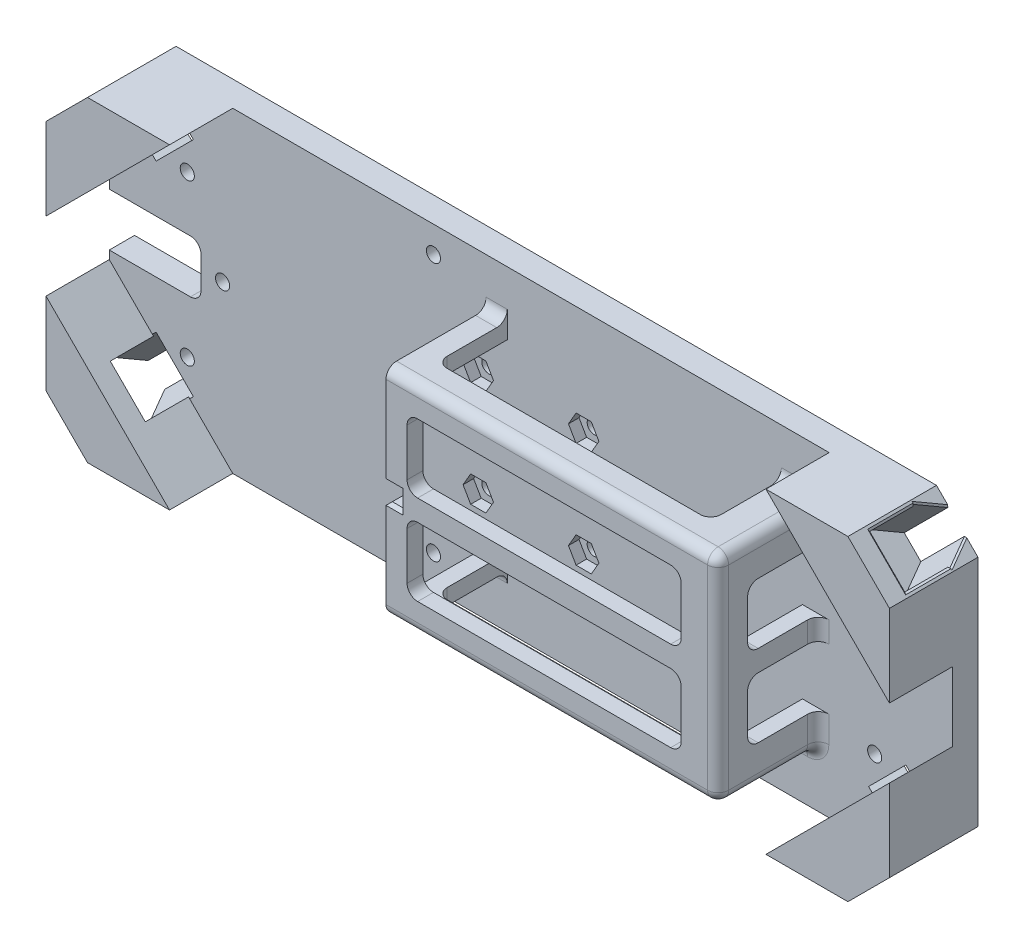
SolidWorks part; units mm, degrees
ref_plane "Front Plane" through (0, 0, 0) normal (0, 0, 1) x (1, 0, 0)
ref_plane "Top Plane" through (0, 0, 0) normal (0, 1, 0) x (1, 0, 0)
ref_plane "Right Plane" through (0, 0, 0) normal (1, 0, 0) x (0, 0, -1)
sketch "Sketch1" plane through (10.8587, 0, 0) normal (0, 0, 1) x (1, 0, 0)
  line L0 (-52.705, 21.59) -> (48.895, 21.59)
  line L1 (52.705, -25.4) -> (-52.705, -25.4)
  line L2 (52.705, -25.4) -> (52.705, 25.4)
  line L3 (52.705, 25.4) -> (-52.705, 25.4)
  line L4 (-52.705, -25.4) -> (-52.705, 25.4)
  line L5 (52.705, -25.4) -> (-52.705, 25.4) construction
  line L6 (52.705, 25.4) -> (-52.705, -25.4) construction
  line L7 (48.895, 21.59) -> (48.895, -22.86)
  line L8 (48.895, -22.86) -> (-52.705, -22.86)
  line L9 (-52.705, 13.97) -> (-6.985, 13.97)
  line L10 (-6.985, 13.97) -> (-6.985, -6.35)
  line L11 (-6.985, -6.35) -> (-52.705, -6.35)
  point P0 (0, 0)
  dimension "D1" = 105.41
  dimension "D2" = 50.8
  dimension "D3" = 101.6
  dimension "D4" = 44.45
  dimension "D5" = 3.81
  dimension "D6" = 45.72
  dimension "D7" = 20.32
  dimension "D8" = 7.62
extrude "Boss-Extrude1" add sketch "Sketch1" along normal blind 27.432 contours L7 L8 L4 L1 L2 L3 L0 region at (-40.6761, 23.495, 0)
extrude "Boss-Extrude2" add sketch "Sketch1<3>" along normal blind 5.08 contours L10 L11 L4 L8 L7 L0 L9 region at (16.19, -1.7862, 0)
sketch "Sketch1<3>" plane through (10.8587, 0, 0) normal (0, 0, 1) x (1, 0, 0) same geometry as "Sketch1"
sketch "Sketch4" plane through (10.8587, 0, 5.08) normal (0, 0, 1) x (1, 0, 0)
  line L0 (-52.705, 21.59) -> (48.895, 21.59) construction
  line L1 (-44.7859, 21.59) -> (-47.9241, 21.59)
  line L2 (-47.9241, 21.59) -> (-49.4932, 18.8722)
  line L3 (-49.4932, 18.8722) -> (-47.9241, 16.1544)
  line L4 (-47.9241, 16.1544) -> (-44.7859, 16.1544)
  line L5 (-44.7859, 16.1544) -> (-43.2168, 18.8722)
  line L6 (-43.2168, 18.8722) -> (-44.7859, 21.59)
  line L7 (-52.705, 13.97) -> (-52.705, 21.59) construction
  line L8 (-13.3987, 22.7847) -> (-13.3987, -11.3368) construction
  line L9 (21.1266, 16.1544) -> (17.9884, 16.1544)
  line L10 (17.9884, 16.1544) -> (16.4193, 18.8722)
  line L11 (16.4193, 18.8722) -> (17.9884, 21.59)
  line L12 (17.9884, 21.59) -> (21.1266, 21.59)
  line L13 (21.1266, 21.59) -> (22.6958, 18.8722)
  line L14 (22.6958, 18.8722) -> (21.1266, 16.1544)
  line L15 (0, 0) -> (10.9329, 0) construction
  line L16 (22.6958, -18.8722) -> (21.1266, -16.1544)
  line L17 (21.1266, -21.59) -> (22.6958, -18.8722)
  line L18 (17.9884, -21.59) -> (21.1266, -21.59)
  line L19 (16.4193, -18.8722) -> (17.9884, -21.59)
  line L20 (17.9884, -16.1544) -> (16.4193, -18.8722)
  line L21 (21.1266, -16.1544) -> (17.9884, -16.1544)
  line L22 (-49.4932, -18.8722) -> (-47.9241, -16.1544)
  line L23 (-47.9241, -21.59) -> (-49.4932, -18.8722)
  line L24 (-43.2168, -18.8722) -> (-44.7859, -21.59)
  line L25 (-44.7859, -16.1544) -> (-43.2168, -18.8722)
  line L26 (-47.9241, -16.1544) -> (-44.7859, -16.1544)
  line L27 (-44.7859, -21.59) -> (-47.9241, -21.59)
  circle A0 centre (-46.355, 18.8722) radius 2.7178 construction
  circle A1 centre (-46.355, 18.8722) radius 1.524
  circle A2 centre (19.5575, 18.8722) radius 1.524
  circle A3 centre (-46.355, -18.8722) radius 1.524
  circle A4 centre (19.5575, -18.8722) radius 1.524
  dimension "D4" = 3.048
  dimension "D1" = 5.4356
  dimension "D2" = 6.35
  dimension "D3" = 2.54
extrude "Cut-Extrude1" cut sketch "Sketch4" against normal blind 2.286 contours L5 L6 L14 L2 L3 L4 A1 | L14 L13 L11 L10 L9 A2 | L26 L22 L23 L12 L24 L25 A3 | L16 L21 L20 L19 L12 L17 A4 region at (-33.2145, 20.1896, 5.08) region at (30.4163, 16.2374, 5.08) region at (32.698, -20.1896, 5.08) region at (-37.778, -17.5548, 5.08)
extrude "Cut-Extrude2" cut sketch "Sketch4<4>" against normal through all contours A1 | A2 | A3 | A4 region at (-35.4963, 18.8722, 5.08) region at (30.4163, 18.8722, 5.08) region at (-35.4963, -18.8722, 5.08) region at (30.4163, -18.8722, 5.08)
sketch "Sketch4<4>" plane through (10.8587, 0, 5.08) normal (0, 0, 1) x (1, 0, 0) same geometry as "Sketch4"
sketch "Sketch7" plane through (10.8587, 0, 27.432) normal (0, 0, 1) x (1, 0, 0)
  line L0 (0, 0) -> (-46.355, 0) construction
  line L1 (-52.705, 25.4) -> (52.705, 25.4)
  line L2 (-52.705, 25.4) -> (-52.705, 6.35)
  line L3 (-52.705, -25.4) -> (52.705, -25.4)
  line L4 (52.705, 25.4) -> (52.705, -25.4)
  line L5 (-52.705, 6.35) -> (-46.355, 6.35)
  line L7 (-52.705, -6.35) -> (-46.355, -6.35)
  line L8 (-46.355, 6.35) -> (-46.355, -6.35)
  line L9 (-52.705, -6.35) -> (-52.705, -25.4)
  line L10 (-28.575, 0) -> (-1035.3573, 0) construction
  point P11 (-46.355, 0)
  dimension "D1" = 12.7
  dimension "D2" = 6.35
extrude "Boss-Extrude3" add sketch "Sketch7" along normal blind 3.81
fillet "Fillet1" radius 2.54 5 edges at (10.8587, -25.4, 31.242) (63.5637, -25.4, 15.621) (63.5637, 0, 31.242) (63.5637, 25.4, 15.621) (10.8587, 25.4, 31.242)
chamfer "Chamfer3" distance 1.27 angle 45 9 edges at (-41.8463, 21.59, 16.256) (-41.8463, -22.86, 16.256) (-41.8463, 13.97, 27.432) (-41.8463, -14.605, 27.432) (-41.8463, -6.35, 29.337) (-38.6713, -6.35, 31.242) (-35.4963, 0, 31.242) (-38.6713, 6.35, 31.242) (-41.8463, 6.35, 29.337)
chamfer "Chamfer4" distance 0.254 angle 45 4 edges at (-33.9723, -18.8722, 0) (31.9403, -18.8722, 0) (-33.9723, 18.8722, 0) (31.9403, 18.8722, 0)
sketch "Sketch8" plane through (10.8587, 0, 5.08) normal (0, 0, 1) x (1, 0, 0)
  line L0 (-52.705, -7.62) -> (-52.705, -22.86) construction
  line L1 (48.895, 21.59) -> (-52.705, 21.59)
  line L2 (48.895, 21.59) -> (48.895, -22.86)
  line L3 (48.895, -22.86) -> (-52.705, -22.86)
  line L4 (-52.705, 21.59) -> (-52.705, -22.86)
  line L5 (48.895, -22.86) -> (-51.435, -22.86) construction
extrude "Cut-Extrude3" cut sketch "Sketch8" against normal up to surface (5.08 mm away) up to face at (-33.7183, -18.8722, 0)
chamfer "Chamfer5" distance 1.27 angle 45 2 edges at (-41.8463, -22.86, 2.54) (-41.8463, 21.59, 2.54)
sketch "Sketch9" plane through (10.8587, 0, 0) normal (0, 0, -1) x (-1, 0, 0)
  line L0 (-90.7413, 28.1) -> (-80.7413, 38.1)
  line L1 (-80.7413, -38.1) -> (102.4587, -38.1)
  line L2 (-90.7413, -28.1) -> (-90.7413, 28.1)
  line L3 (-80.7413, 38.1) -> (102.4587, 38.1)
  line L4 (112.4587, -28.1) -> (112.4587, 28.1)
  line L5 (-90.7413, -38.1) -> (112.4587, 38.1) construction
  line L6 (-90.7413, 38.1) -> (112.4587, -38.1) construction
  line L7 (-90.7413, -28.1) -> (-80.7413, -38.1)
  line L8 (102.4587, 38.1) -> (112.4587, 28.1)
  line L9 (102.4587, -38.1) -> (112.4587, -28.1)
  point P0 (10.8587, 0)
  dimension "D1" = 203.2
  dimension "D2" = 76.2
extrude "Boss-Extrude4" add sketch "Sketch9" along normal blind 6.096
fillet "Fillet2" radius 1.27 5 edges at (9.5887, -25.4, 0) (62.8198, -24.6561, 0) (63.5637, 0, 0) (62.8198, 24.6561, 0) (9.5887, 25.4, 0)
sketch "Sketch11" plane through (0, 0, 0) normal (0, 0, 1) x (1, 0, 0)
  line L0 (-101.6, 28.1) -> (-91.6, 38.1)
  line L1 (-91.6, 38.1) -> (-84.9257, 38.1)
  line L4 (-101.6, -28.1) -> (-101.6, 28.1) construction
  line L5 (-101.6, 21.4257) -> (-101.6, 28.1)
  line L6 (0, 0) -> (0, 53.0626) construction
  line L7 (-1000, 0) -> (0, 0) construction
  line L25 (-76.5885, 29.7628) -> (-93.2628, 13.0885)
  line L26 (-84.9257, 38.1) -> (-76.5885, 29.7628)
  line L28 (-101.6, 21.4257) -> (-93.2628, 13.0885)
  line L54 (0, -17.1831) -> (0, 17.1831) construction
  line L55 (84.9257, 38.1) -> (76.5885, 29.7628)
  line L56 (91.6, 38.1) -> (84.9257, 38.1)
  line L57 (101.6, 28.1) -> (91.6, 38.1)
  line L58 (101.6, 21.4257) -> (101.6, 28.1)
  line L59 (101.6, 21.4257) -> (93.2628, 13.0885)
  line L60 (76.5885, 29.7628) -> (93.2628, 13.0885)
  line L61 (17.1831, 0) -> (-17.1831, 0) construction
  line L62 (91.6, -38.1) -> (84.9257, -38.1)
  line L63 (101.6, -28.1) -> (91.6, -38.1)
  line L64 (101.6, -21.4257) -> (101.6, -28.1)
  line L65 (101.6, -21.4257) -> (93.2628, -13.0885)
  line L66 (76.5885, -29.7628) -> (93.2628, -13.0885)
  line L67 (84.9257, -38.1) -> (76.5885, -29.7628)
  line L68 (-84.9257, -38.1) -> (-76.5885, -29.7628)
  line L69 (-91.6, -38.1) -> (-84.9257, -38.1)
  line L70 (-101.6, -28.1) -> (-91.6, -38.1)
  line L71 (-101.6, -21.4257) -> (-101.6, -28.1)
  line L72 (-101.6, -21.4257) -> (-93.2628, -13.0885)
  line L73 (-76.5885, -29.7628) -> (-93.2628, -13.0885)
  dimension "D1" = 16.51
  dimension "D2" = 8.3372
extrude "Boss-Extrude5" [suppressed] add sketch "Sketch11" along normal blind 19.05
sketch "Sketch13" plane through (-64.85, 64.85, 0) normal (-0.7071, 0.7071, 0) x (0, 0, 1)
  line L0 (-6.096, -44.9013) -> (-6.096, -42.0708)
  line L1 (-6.096, -51.9723) -> (-6.096, -37.8302) construction
  line L2 (-6.096, -42.0708) -> (0, -38.5513)
  line L3 (0, -38.5513) -> (0, -51.2513)
  line L4 (0, -51.2513) -> (-6.096, -47.7318)
  line L5 (-6.096, -47.7318) -> (-6.096, -44.9013)
  dimension "D1" = 6.096
  dimension "D2" = 120
  dimension "D3" = 120
  dimension "D4" = 12.7
extrude "Cut-Extrude4" cut sketch "Sketch13" against normal blind 15.24
mirror "Mirror2" about plane through (0, 0, 0) normal (0, 1, 0) of "Cut-Extrude4"
mirror "Mirror3" about plane through (0, 0, 0) normal (1, 0, 0) of "Cut-Extrude4", "Mirror2"
chamfer "Chamfer7" distance 0.381 angle 45 8 edges at (99.8458, -29.8542, -3.048) (93.3542, -36.3458, -3.048) (93.3542, 36.3458, -3.048) (99.8458, 29.8542, -3.048) (-93.3542, 36.3458, -3.048) (-99.8458, 29.8542, -3.048) (-93.3542, -36.3458, -3.048) (-99.8458, -29.8542, -3.048)
sketch "Sketch17" [suppressed] plane through (0, 0, 19.05) normal (0, 0, 1) x (1, 0, 0)
  line L0 (-96.6, 33.1) -> (-92.1099, 37.5901)
  line L1 (-91.6, 38.1) -> (-101.6, 28.1) construction
  line L3 (20.6756, 0) -> (-20.6756, 0) construction
  line L6 (-80.4355, -25.9158) -> (-89.4158, -16.9355)
  line L8 (-101.0901, 28.6099) -> (-96.6, 33.1)
  line L10 (-92.1099, -37.5901) -> (-80.4355, -25.9158)
  line L30 (-92.1099, 37.5901) -> (-80.4355, 25.9158)
  line L31 (-93.2628, 13.0885) -> (-76.5885, 29.7628) construction
  line L32 (-80.4355, 25.9158) -> (-89.4158, 16.9355)
  line L33 (-89.4158, 16.9355) -> (-101.0901, 28.6099)
  line L34 (-96.6, -33.1) -> (-92.1099, -37.5901)
  line L35 (-101.0901, -28.6099) -> (-96.6, -33.1)
  line L36 (-89.4158, -16.9355) -> (-101.0901, -28.6099)
  line L37 (0, -20.6756) -> (0, 20.6756) construction
  line L38 (92.1099, -37.5901) -> (80.4355, -25.9158)
  line L39 (96.6, -33.1) -> (92.1099, -37.5901)
  line L40 (101.0901, -28.6099) -> (96.6, -33.1)
  line L41 (89.4158, -16.9355) -> (101.0901, -28.6099)
  line L42 (80.4355, -25.9158) -> (89.4158, -16.9355)
  line L43 (80.4355, 25.9158) -> (89.4158, 16.9355)
  line L44 (92.1099, 37.5901) -> (80.4355, 25.9158)
  line L45 (96.6, 33.1) -> (92.1099, 37.5901)
  line L46 (101.0901, 28.6099) -> (96.6, 33.1)
  line L47 (89.4158, 16.9355) -> (101.0901, 28.6099)
  dimension "D1" = 12.7
extrude "Cut-Extrude7" [suppressed] cut sketch "Sketch17" against normal blind 10.922
sketch "Sketch18" [suppressed] plane through (0, 0, 8.128) normal (0, 0, 1) x (1, 0, 0)
  line L0 (-92.1099, 37.5901) -> (-101.0901, 28.6099) construction
  line L1 (-80.4355, 25.9158) -> (-92.1099, 37.5901) construction
  circle A0 centre (-89.4158, 25.9158) radius 1.778
  dimension "D1" = 3.556
  dimension "D2" = 10.16
  dimension "D3" = 6.35
extrude "Cut-Extrude8" [suppressed] cut sketch "Sketch18" against normal up to surface (8.382 mm away)
mirror "Mirror6" [suppressed] about plane through (0, 0, 0) normal (0, 1, 0)
mirror "Mirror7" [suppressed] about plane through (0, 0, 0) normal (1, 0, 0)
sketch "Sketch19" plane through (0, 0, 31.242) normal (0, 0, 1) x (1, 0, 0)
  line L1 (-67.9348, -33.6729) -> (67.9348, -33.6729)
  line L2 (-67.9348, -33.6729) -> (-67.9348, 33.6729)
  line L3 (-67.9348, 33.6729) -> (67.9348, 33.6729)
  line L4 (67.9348, -33.6729) -> (67.9348, 33.6729)
  line L5 (-67.9348, -33.6729) -> (67.9348, 33.6729) construction
  line L6 (-67.9348, 33.6729) -> (67.9348, -33.6729) construction
  point P0 (0, 0)
extrude "Cut-Extrude9" cut sketch "Sketch19" against normal up to surface (31.242 mm away) up to face at (0, 0, 0)
sketch "Sketch20" plane through (0, 0, 0) normal (0, 0, 1) x (1, 0, 0)
  line L0 (65.405, 22.86) -> (65.405, -21.59)
  line L1 (65.405, -21.59) -> (-10.795, -21.59)
  line L2 (65.405, 22.86) -> (-10.795, 22.86)
  line L3 (-10.795, 22.86) -> (-10.795, 26.67)
  line L4 (-10.795, 26.67) -> (69.215, 26.67)
  line L5 (69.215, 26.67) -> (69.215, -25.4)
  line L6 (69.215, -25.4) -> (-10.795, -25.4)
  line L7 (-10.795, -25.4) -> (-10.795, -21.59)
  line L8 (101.6, 28.1) -> (101.6, -28.1) construction
  line L9 (91.6, -38.1) -> (-91.6, -38.1) construction
  dimension "D1" = 52.07
  dimension "D2" = 44.45
  dimension "D3" = 3.81
  dimension "D4" = 80.01
  dimension "D5" = 76.2
  dimension "D6" = 32.385
  dimension "D7" = 12.7
extrude "Boss-Extrude6" add sketch "Sketch20" along normal blind 20.32
sketch "Sketch21" plane through (0, 0, 20.32) normal (0, 0, 1) x (1, 0, 0)
  line L1 (-10.795, 26.67) -> (69.215, 26.67)
  line L2 (-10.795, 26.67) -> (-10.795, -25.4)
  line L3 (-10.795, -25.4) -> (69.215, -25.4)
  line L4 (69.215, 26.67) -> (69.215, -25.4)
extrude "Boss-Extrude7" add sketch "Sketch21" along normal blind 3.81
fillet "Fillet3" radius 2.54 8 edges at (29.21, 26.67, 0) (69.215, 0.635, 0) (29.21, 26.67, 24.13) (69.215, 26.67, 12.065) (69.215, 0.635, 24.13) (69.215, -25.4, 12.065) (29.21, -25.4, 0) (29.21, -25.4, 24.13)
chamfer "Chamfer8" distance 1.27 angle 45 3 edges at (-10.795, -21.59, 10.16) (-10.795, 22.86, 10.16) (-10.795, 0.635, 20.32)
chamfer "Chamfer9" [suppressed] distance 0.254 angle 45
sketch "Sketch22" [suppressed] plane through (0, 0, -0.254) normal (0, 0, -1) x (-1, 0, 0)
  line L0 (-91.6432, -38.0568) -> (-101.5568, -28.1432) construction
  line L1 (-85.0164, -25.9158) -> (-87.2161, -22.1058)
  line L2 (-87.2161, -22.1058) -> (-91.6155, -22.1058)
  line L3 (-91.6155, -22.1058) -> (-93.8152, -25.9158)
  line L4 (-93.8152, -25.9158) -> (-91.6155, -29.7258)
  line L5 (-91.6155, -29.7258) -> (-87.2161, -29.7258)
  line L6 (-87.2161, -29.7258) -> (-85.0164, -25.9158)
  circle A0 centre (-89.4158, -25.9158) radius 3.81 construction
  circle A1 centre (-89.4158, -25.9158) radius 1.778 construction
  dimension "D1" = 7.62
  dimension "D2" = 10.16
  dimension "D3" = 0
extrude "Cut-Extrude10" [suppressed] cut sketch "Sketch22" against normal blind 3.302
mirror "Mirror8" [suppressed] about plane through (0, 0, 0) normal (0, 1, 0)
mirror "Mirror9" [suppressed] about plane through (0, 0, 0) normal (1, 0, 0)
sketch "Sketch23" plane through (0, 0, 0) normal (0, 0, 1) x (1, 0, 0)
  line L16 (90.3138, -17.8336) -> (100.8207, -28.3405)
  line L18 (-91.6, -38.1) -> (91.6, -38.1)
  line L19 (100.8207, -28.3405) -> (101.4012, -28.2988)
  line L20 (100.8207, -28.3405) -> (101.4012, -28.2988)
  line L22 (101.6, -28.1) -> (101.6, 28.1)
  line L26 (91.6, 38.1) -> (-91.6, 38.1)
  line L27 (101.4012, 28.2988) -> (100.8207, 28.3405)
  line L28 (101.4012, 28.2988) -> (100.8207, 28.3405)
  line L29 (90.3138, -17.8336) -> (100.8207, -28.3405)
  line L30 (-101.6, 28.1) -> (-101.6, -28.1)
  line L34 (-91.6, -38.1) -> (91.6, -38.1)
  line L38 (101.6, -28.1) -> (101.6, 28.1)
  line L42 (91.6, 38.1) -> (-91.6, 38.1)
  line L46 (-101.6, 28.1) -> (-101.6, -28.1)
  line L56 (91.8405, 37.3207) -> (91.7988, 37.9012)
  line L57 (91.8405, 37.3207) -> (91.7988, 37.9012)
  line L62 (-91.7988, 37.9012) -> (-91.8405, 37.3207)
  line L63 (-91.7988, 37.9012) -> (-91.8405, 37.3207)
  line L64 (100.8207, 28.3405) -> (90.3138, 17.8336)
  line L66 (-100.8207, 28.3405) -> (-101.4012, 28.2988)
  line L67 (-100.8207, 28.3405) -> (-101.4012, 28.2988)
  line L72 (-101.4012, -28.2988) -> (-100.8207, -28.3405)
  line L73 (-101.4012, -28.2988) -> (-100.8207, -28.3405)
  line L74 (100.8207, 28.3405) -> (90.3138, 17.8336)
  line L76 (-91.8405, -37.3207) -> (-91.7988, -37.9012)
  line L77 (-91.8405, -37.3207) -> (-91.7988, -37.9012)
  line L82 (91.7988, -37.9012) -> (91.8405, -37.3207)
  line L83 (91.7988, -37.9012) -> (91.8405, -37.3207)
  line L84 (101.4012, -28.2988) -> (101.6, -28.1)
  line L85 (101.4012, -28.2988) -> (101.6, -28.1)
  line L86 (101.6, 28.1) -> (101.4012, 28.2988)
  line L87 (101.6, 28.1) -> (101.4012, 28.2988)
  line L88 (91.7988, 37.9012) -> (91.6, 38.1)
  line L89 (91.7988, 37.9012) -> (91.6, 38.1)
  line L90 (-91.6, 38.1) -> (-91.7988, 37.9012)
  line L91 (-91.6, 38.1) -> (-91.7988, 37.9012)
  line L92 (90.3138, 17.8336) -> (81.3336, 26.8138)
  line L93 (90.3138, 17.8336) -> (81.3336, 26.8138)
  line L94 (81.3336, 26.8138) -> (91.8405, 37.3207)
  line L95 (81.3336, 26.8138) -> (91.8405, 37.3207)
  line L96 (-91.8405, 37.3207) -> (-81.3336, 26.8138)
  line L97 (-91.8405, 37.3207) -> (-81.3336, 26.8138)
  line L98 (-81.3336, 26.8138) -> (-90.3138, 17.8336)
  line L99 (-81.3336, 26.8138) -> (-90.3138, 17.8336)
  line L100 (-90.3138, 17.8336) -> (-100.8207, 28.3405)
  line L101 (-90.3138, 17.8336) -> (-100.8207, 28.3405)
  line L102 (-100.8207, -28.3405) -> (-90.3138, -17.8336)
  line L103 (-100.8207, -28.3405) -> (-90.3138, -17.8336)
  line L104 (-90.3138, -17.8336) -> (-81.3336, -26.8138)
  line L105 (-90.3138, -17.8336) -> (-81.3336, -26.8138)
  line L106 (-81.3336, -26.8138) -> (-91.8405, -37.3207)
  line L107 (-81.3336, -26.8138) -> (-91.8405, -37.3207)
  line L108 (91.8405, -37.3207) -> (81.3336, -26.8138)
  line L109 (91.8405, -37.3207) -> (81.3336, -26.8138)
  line L110 (81.3336, -26.8138) -> (90.3138, -17.8336)
  line L111 (81.3336, -26.8138) -> (90.3138, -17.8336)
  line L112 (-101.4012, 28.2988) -> (-101.6, 28.1)
  line L113 (-101.4012, 28.2988) -> (-101.6, 28.1)
  line L114 (-101.6, -28.1) -> (-101.4012, -28.2988)
  line L115 (-101.6, -28.1) -> (-101.4012, -28.2988)
  line L116 (-91.7988, -37.9012) -> (-91.6, -38.1)
  line L117 (-91.7988, -37.9012) -> (-91.6, -38.1)
  line L118 (91.6, -38.1) -> (91.7988, -37.9012)
  line L119 (91.6, -38.1) -> (91.7988, -37.9012)
  dimension "D1" = 0
sketch "Sketch24" plane through (0, 0, 0) normal (0, 0, 1) x (1, 0, 0)
  line L10 (-90.9424, 19.001) -> (-101.6, 8.3434)
  line L11 (-101.6, -28.1) -> (-101.6, 28.1) construction
  line L12 (-101.6, 8.3434) -> (-101.6, 28.1)
  line L13 (-101.6, 28.1) -> (-100.8207, 28.8793)
  line L14 (-100.8207, 28.8793) -> (-90.9424, 19.001)
  line L15 (-92.7385, 36.9615) -> (-91.6, 38.1)
  line L16 (-91.6, 38.1) -> (-71.8434, 38.1)
  line L17 (-91.6, 38.1) -> (91.6, 38.1) construction
  line L18 (-71.8434, 38.1) -> (-82.8602, 27.0832)
  line L19 (-82.8602, 27.0832) -> (-92.7385, 36.9615)
extrude "Boss-Extrude8" add sketch "Sketch24" along normal blind 10.16
sketch "Sketch26" plane through (0, 0, 10.16) normal (0, 0, 1) x (1, 0, 0)
  line L0 (-101.6, 8.3434) -> (-71.8434, 38.1)
  line L1 (-71.8434, 38.1) -> (-91.6, 38.1)
  line L2 (-91.6, 38.1) -> (-101.6, 28.1)
  line L3 (-101.6, 28.1) -> (-101.6, 8.3434)
extrude "Boss-Extrude10" add sketch "Sketch26" along normal blind 5.08
mirror "Mirror12" about plane through (0, 0, 0) normal (0, 1, 0) of "Boss-Extrude8", "Boss-Extrude10"
mirror "Mirror13" about plane through (0, 0, 0) normal (1, 0, 0) of "Mirror12"
sketch "Sketch27" plane through (0, 0, 0) normal (0, 0, 1) x (1, 0, 0)
  circle A0 centre (-23.495, 31.75) radius 1.7
  circle A1 centre (-23.495, -30.48) radius 1.7
extrude "Cut-Extrude11" cut sketch "Sketch27" against normal up to next
sketch "Sketch28" plane through (0, 0, -6.096) normal (0, 0, -1) x (-1, 0, 0)
  circle A0 centre (23.495, -30.48) radius 3.302
  circle A1 centre (23.495, 31.75) radius 3.302
  dimension "D1" = 6.604
extrude "Cut-Extrude12" cut sketch "Sketch28" against normal blind 3.302
sketch "Sketch29" plane through (0, 0, 24.13) normal (0, 0, 1) x (1, 0, 0)
  line L0 (-10.795, 24.13) -> (-10.795, -22.86) construction
  line L1 (-5.715, 19.685) -> (60.325, 19.685)
  line L2 (-5.715, 19.685) -> (-5.715, 3.175)
  line L3 (-5.715, -18.415) -> (60.325, -18.415)
  line L4 (60.325, 19.685) -> (60.325, 3.175)
  line L6 (66.675, -22.86) -> (66.675, 24.13) construction
  line L7 (-10.795, -22.86) -> (66.675, -22.86) construction
  line L8 (-5.715, -1.905) -> (-5.715, -18.415)
  line L9 (-5.715, 3.175) -> (60.325, 3.175)
  line L11 (-5.715, -1.905) -> (60.325, -1.905)
  line L13 (60.325, -1.905) -> (60.325, -18.415)
  dimension "D1" = 38.1
  dimension "D2" = 6.35
  dimension "D3" = 5.08
  dimension "D4" = 4.445
  dimension "D5" = 5.08
extrude "Cut-Extrude13" cut sketch "Sketch29" against normal up to next
sketch "Sketch30" plane through (0, -25.4, 0) normal (0, -1, 0) x (1, 0, 0)
  line L0 (71.8434, 0) -> (-71.8434, 0) construction
  line L1 (-5.715, 0) -> (60.325, 0)
  line L2 (-5.715, 0) -> (-5.715, 17.018)
  line L3 (-5.715, 17.018) -> (60.325, 17.018)
  line L4 (60.325, 0) -> (60.325, 17.018)
  line L5 (-10.795, 21.59) -> (-10.795, 2.54) construction
  line L6 (66.675, 2.54) -> (66.675, 21.59) construction
  line L7 (66.675, 21.59) -> (-10.795, 21.59) construction
  dimension "D1" = 5.08
  dimension "D2" = 6.35
  dimension "D3" = 4.572
extrude "Cut-Extrude14" cut sketch "Sketch30" against normal through all
sketch "Sketch31" plane through (69.215, 0, 0) normal (1, 0, 0) x (0, 0, -1)
  line L0 (-21.59, 24.13) -> (-21.59, -22.86) construction
  line L1 (-17.018, 17.78) -> (0, 17.78)
  line L2 (-17.018, 17.78) -> (-17.018, 3.175)
  line L3 (-17.018, -16.51) -> (0, -16.51)
  line L4 (0, 17.78) -> (0, 3.175)
  line L5 (0, 8.3434) -> (0, -8.3434) construction
  line L6 (-2.54, 24.13) -> (-21.59, 24.13) construction
  line L7 (-21.59, -22.86) -> (-2.54, -22.86) construction
  line L9 (-17.018, -1.905) -> (0, -1.905)
  line L11 (-17.018, 3.175) -> (0, 3.175)
  line L15 (-17.018, -1.905) -> (-17.018, -16.51)
  line L16 (0, -1.905) -> (0, -16.51)
  point P12 (-17.018, 0.635)
  dimension "D1" = 4.572
  dimension "D2" = 0
  dimension "D3" = 6.35
  dimension "D4" = 6.35
  dimension "D5" = 5.08
extrude "Cut-Extrude15" cut sketch "Sketch31" against normal up to next
sketch "Sketch32" plane through (0, -25.4, 0) normal (0, 1, 0) x (1, 0, 0)
  line L1 (-5.715, 0) -> (60.325, 0)
  line L2 (-5.715, 0) -> (-5.715, -2.54)
  line L3 (-5.715, -2.54) -> (60.325, -2.54)
  line L4 (60.325, 0) -> (60.325, -2.54)
extrude "Cut-Extrude16" cut sketch "Sketch32" against normal through all
sketch "Sketch33" plane through (69.215, 0, 0) normal (-1, 0, 0) x (0, 0, 1)
  line L0 (17.018, 17.78) -> (0, 17.78) construction
  line L1 (2.6099, 17.78) -> (0, 17.78)
  line L2 (2.6099, 17.78) -> (2.6099, -16.51)
  line L3 (2.6099, -16.51) -> (0, -16.51)
  line L4 (0, 17.78) -> (0, -16.51)
  line L5 (0, -16.51) -> (17.018, -16.51) construction
  point P6 (1.3049, -16.51)
  dimension "D1" = 0
  dimension "D2" = 0
extrude "Cut-Extrude17" cut sketch "Sketch33" against normal blind 3.302
sketch "Sketch34" plane through (0, 0, 0) normal (0, 0, 1) x (1, 0, 0)
  circle A0 centre (-74.295, 0.635) radius 1.7
extrude "Cut-Extrude18" cut sketch "Sketch34" against normal through all
sketch "Sketch35" plane through (0, 0, -6.096) normal (0, 0, -1) x (-1, 0, 0)
  circle A0 centre (74.295, 0.635) radius 3.302
  dimension "D1" = 6.604
extrude "Cut-Extrude19" cut sketch "Sketch35" against normal blind 3.302
fillet "Fillet4" radius 2.54 17 edges at (-5.715, 3.175, 22.225) (-5.715, -18.415, 22.225) (60.325, 3.175, 22.225) (60.325, -18.415, 22.225) (60.325, -1.905, 22.225) (60.325, 19.685, 22.225) (-5.715, 19.685, 22.225) (-5.715, -1.905, 22.225) (-5.715, -23.495, 17.018) (60.325, -23.495, 17.018) (-5.715, 24.765, 17.018) (60.325, 24.765, 17.018) (67.31, -16.51, 17.018) (67.31, 3.175, 17.018) (67.31, 17.78, 17.018) (67.31, -1.905, 17.018) (69.215, 0.635, 0)
hole_wizard "CBORE for M3 SHCS1" positions "Sketch36" profile "Sketch37" counterbore size "M3" standard "ANSI Metric" end condition up to next
sketch "Sketch36" plane through (0, 0, -6.096) normal (0, 0, -1) x (-1, 0, 0)
  line L0 (-91.6, -38.1) -> (91.6, -38.1) construction
  line L1 (101.6, -28.1) -> (101.6, 28.1) construction
  point P0 (82.804, -19.304)
  dimension "D1" = 18.796
  dimension "D2" = 18.796
sketch "Sketch37" plane through (-82.804, -19.304, -6.096) normal (1, 0, 0) x (0, 1, 0)
  line L0 (0, 0) -> (0, 6.097)
  line L1 (0, 6.097) -> (1.7, 6.097)
  line L3 (1.7, 6.097) -> (1.7, 3)
  line L4 (1.7, 3) -> (3.25, 3)
  line L5 (3.25, 3) -> (3.25, 0)
  line L7 (3.25, 0) -> (0, 0)
  line L11 (0, -6.35) -> (0, 107.95) construction
  dimension "Thru Hole Dia." = 3.4
  dimension "Thru Hole Depth" = 6.097
  dimension "C'Bore Dia." = 6.5
  dimension "C'Bore Depth" = 3
mirror "Mirror14" about plane through (0, 0, 0) normal (0, 1, 0) of "CBORE for M3 SHCS1"
mirror "Mirror15" about plane through (0, 0, 0) normal (1, 0, 0) of "Mirror14"
sketch "Sketch38" plane through (0, 0, -6.096) normal (0, 0, -1) x (-1, 0, 0)
  line L1 (-5.715, -3.81) -> (5.715, -3.81)
  line L2 (-5.715, -3.81) -> (-5.715, 3.81)
  line L3 (-5.715, 3.81) -> (5.715, 3.81)
  line L4 (5.715, -3.81) -> (5.715, 3.81)
  line L5 (-5.715, -3.81) -> (5.715, 3.81) construction
  line L6 (-5.715, 3.81) -> (5.715, -3.81) construction
  point P0 (0, 0)
  dimension "D1" = 11.43
  dimension "D2" = 7.62
extrude "Cut-Extrude20" cut sketch "Sketch38" against normal up to next
chamfer "Chamfer10" distance 0.762 angle 45 4 edges at (0, -3.81, -6.096) (5.715, 0, -6.096) (0, 3.81, -6.096) (-5.715, 0, -6.096)
hole_wizard "M3 Clearance Hole1" positions "Sketch39" profile "Sketch40" hole size "M3" standard "ANSI Metric" end condition up to next
sketch "Sketch39" plane through (0, 0, -6.096) normal (0, 0, -1) x (-1, 0, 0)
  line L0 (16.6243, 0) -> (-16.6243, 0) construction
  line L2 (0, 16.6243) -> (0, -16.6243) construction
  point P0 (12.7, 12.7)
  dimension "D1" = 12.7
  dimension "D2" = 12.7
sketch "Sketch40" plane through (-12.7, 12.7, -6.096) normal (1, 0, 0) x (0, 1, 0)
  line L0 (0, 0) -> (0, 6.097)
  line L1 (0, 6.097) -> (1.7, 6.097)
  line L2 (1.7, 6.097) -> (1.7, 0)
  line L5 (1.7, 0) -> (0, 0)
  line L11 (0, -6.35) -> (0, 107.95) construction
  dimension "Thru Hole Dia." = 3.4
  dimension "Thru Hole Depth" = 6.097
mirror "Mirror16" about plane through (0, 0, 0) normal (0, 1, 0) of "M3 Clearance Hole1"
mirror "Mirror17" about plane through (0, 0, 0) normal (1, 0, 0) of "Mirror16"
sketch "Sketch42" plane through (0, 0, 0) normal (0, 0, 1) x (1, 0, 0)
  line L1 (16.3662, 12.7) -> (14.5331, 15.875)
  line L2 (14.5331, 15.875) -> (10.8669, 15.875)
  line L3 (10.8669, 15.875) -> (9.0338, 12.7)
  line L4 (9.0338, 12.7) -> (10.8669, 9.525)
  line L5 (10.8669, 9.525) -> (14.5331, 9.525)
  line L6 (14.5331, 9.525) -> (16.3662, 12.7)
  circle A0 centre (12.7, 12.7) radius 3.175 construction
  dimension "D1" = 6.35
extrude "Cut-Extrude21" cut sketch "Sketch42" against normal blind 2.54
mirror "Mirror18" about plane through (0, 0, 0) normal (1, 0, 0) of "Cut-Extrude21"
mirror "Mirror19" about plane through (0, 0, 0) normal (0, 1, 0) of "Mirror18"
sketch "Sketch43" plane through (0, 0, 24.13) normal (0, 0, 1) x (1, 0, 0)
  line L0 (-10.795, 24.13) -> (-10.795, -22.86) construction
  line L1 (-14.097, -1.397) -> (-7.493, -1.397)
  line L2 (-14.097, -1.397) -> (-14.097, 2.667)
  line L3 (-14.097, 2.667) -> (-7.493, 2.667)
  line L4 (-7.493, -1.397) -> (-7.493, 2.667)
  line L5 (-14.097, -1.397) -> (-7.493, 2.667) construction
  line L6 (-14.097, 2.667) -> (-7.493, -1.397) construction
  point P0 (-10.795, 0.635)
  dimension "D1" = 6.604
  dimension "D2" = 4.064
extrude "Cut-Extrude22" cut sketch "Sketch43" against normal up to next
chamfer "Chamfer11" distance 0.762 angle 45 5 edges at (-10.795, -1.397, 22.86) (-9.144, -1.397, 24.13) (-7.493, 0.635, 24.13) (-9.144, 2.667, 24.13) (-10.795, 2.667, 22.86)
sketch "Sketch44" plane through (0, 0, 0) normal (0, 0, 1) x (1, 0, 0)
  line L0 (-101.6, -8.3434) -> (-101.6, 8.3434) construction
  line L1 (-123.698, -6.35) -> (-79.502, -6.35)
  line L2 (-123.698, -6.35) -> (-123.698, 6.35)
  line L3 (-123.698, 6.35) -> (-79.502, 6.35)
  line L4 (-79.502, -6.35) -> (-79.502, 6.35)
  line L5 (-123.698, -6.35) -> (-79.502, 6.35) construction
  line L6 (-123.698, 6.35) -> (-79.502, -6.35) construction
  point P0 (-101.6, 0)
  dimension "D1" = 12.7
  dimension "D2" = 44.196
extrude "Cut-Extrude23" cut sketch "Sketch44" against normal through all
sketch "Sketch45" plane through (-64.85, 64.85, 0) normal (-0.7071, 0.7071, 0) x (0, 0, 1)
  line L0 (-6.096, -42.0708) -> (-6.096, -47.7318) construction
  line L1 (0, -50.8703) -> (10.414, -50.8703)
  line L2 (0, -50.8703) -> (0, -38.9323)
  line L3 (0, -38.9323) -> (10.414, -38.9323)
  line L4 (10.414, -50.8703) -> (10.414, -38.9323)
  line L5 (0, -50.8703) -> (10.414, -38.9323) construction
  line L6 (0, -38.9323) -> (10.414, -50.8703) construction
  line L7 (0, -91.7117) -> (0, 37.8302) construction
  point P0 (5.207, -44.9013)
  point P5 (0, -44.9013)
  point P8 (-6.096, -44.9013)
  dimension "D1" = 11.938
  dimension "D2" = 10.414
extrude "Cut-Extrude24" cut sketch "Sketch45" against normal up to next
mirror "Mirror20" about plane through (0, 0, 0) normal (0, 1, 0) of "Cut-Extrude24"
mirror "Mirror21" about plane through (0, 0, 0) normal (1, 0, 0) of "Mirror20"
chamfer "Chamfer12" distance 0.508 angle 44 12 edges at (-92.3793, -37.3207, 5.207) (-100.8207, -28.8793, 5.207) (-96.6, -33.1, 10.414) (92.3793, -37.3207, 5.207) (100.8207, -28.8793, 5.207) (96.6, -33.1, 10.414) (92.3793, 37.3207, 5.207) (100.8207, 28.8793, 5.207) (96.6, 33.1, 10.414) (-100.8207, 28.8793, 5.207) (-92.3793, 37.3207, 5.207) (-96.6, 33.1, 10.414) first distance on face at (-87.4401, -32.3816, 5.207) first distance on face at (-95.8816, -23.9401, 5.207) first distance on face at (-91.6609, -28.1609, 10.414) first distance on face at (96.6, -33.1, 2.2437) first distance on face at (87.4401, 32.3816, 5.207) first distance on face at (95.8816, 23.9401, 5.207) first distance on face at (91.6609, 28.1609, 10.414) first distance on face at (-96.6, 33.1, 2.2437)
fillet "Fillet5" radius 2.54 2 edges at (-79.502, 6.35, -3.048) (-79.502, -6.35, -3.048)
